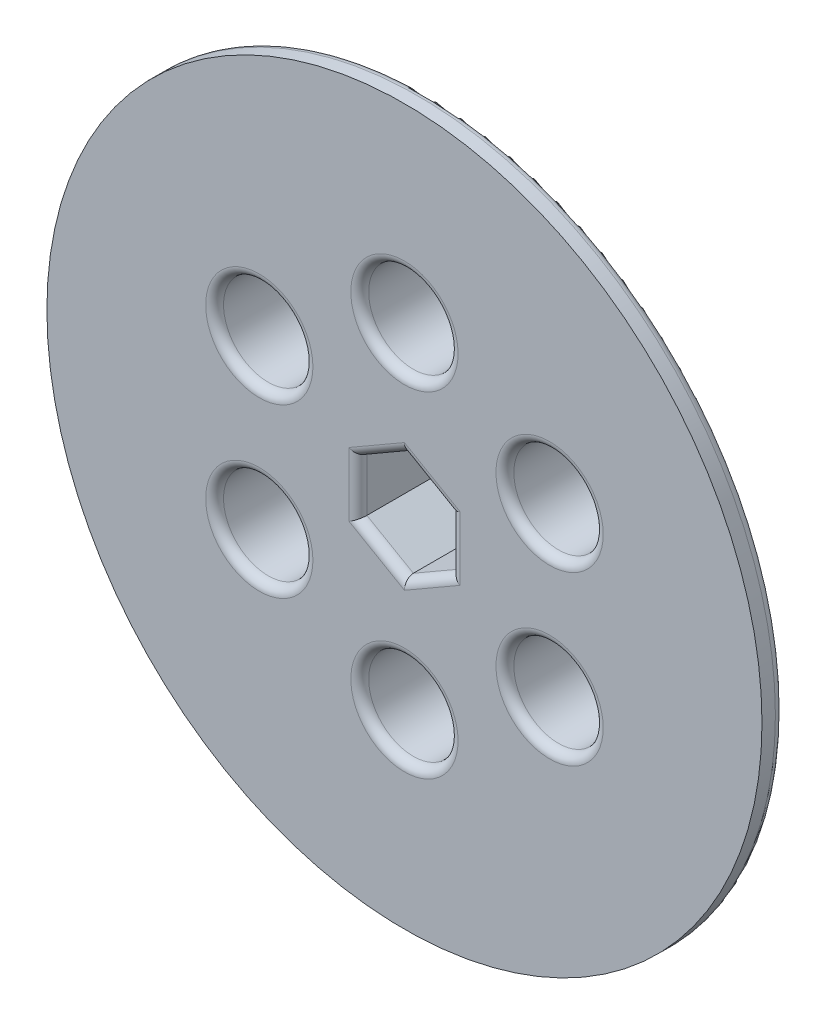
SolidWorks part; units mm, degrees
ref_plane "Front" through (0, 0, 0) normal (0, 0, 1) x (1, 0, 0)
ref_plane "Top" through (0, 0, 0) normal (0, 1, 0) x (1, 0, 0)
ref_plane "Right" through (0, 0, 0) normal (1, 0, 0) x (0, 0, -1)
sketch "Sketch1" plane through (0, 0, 0) normal (0, 0, 1) x (1, 0, 0)
  circle A0 centre (0, 0) radius 31.75
  dimension "D1" = 63.5
extrude "Boss-Extrude1" add sketch "Sketch1" along normal blind 12.7
sketch "Sketch2" plane through (0, 0, 12.7) normal (0, 0, 1) x (1, 0, 0)
  circle A1 centre (0, 0) radius 50.8
  circle A2 centre (0, 0) radius 31.75 construction
  dimension "D1" = 19.05
extrude "Boss-Extrude2" add sketch "Sketch2" along normal blind 3.175
sketch "Sketch3" plane through (0, 0, 0) normal (0, 0, -1) x (-1, 0, 0)
  line L0 (0, 0) -> (0, 23.8125) construction
  line L2 (0, 7.6256) -> (-6.604, 3.8128)
  line L3 (-6.604, 3.8128) -> (-6.604, -3.8128)
  line L4 (-6.604, -3.8128) -> (0, -7.6256)
  line L5 (0, -7.6256) -> (6.604, -3.8128)
  line L6 (6.604, -3.8128) -> (6.604, 3.8128)
  line L7 (6.604, 3.8128) -> (0, 7.6256)
  circle A0 centre (0, 23.8125) radius 2.667
  circle A1 centre (20.6222, 11.9063) radius 2.667
  circle A2 centre (20.6222, -11.9062) radius 2.667
  circle A3 centre (0, -23.8125) radius 2.667
  circle A4 centre (-20.6222, -11.9063) radius 2.667
  circle A5 centre (-20.6222, 11.9062) radius 2.667
  circle A6 centre (0, 0) radius 6.604 construction
  point P17 (0, 0)
  dimension "D2" = 5.334
  dimension "D1" = 23.8125
  dimension "D3" = 6
extrude "r" cut sketch "Sketch3" against normal up to next
sketch "Sketch4" plane through (0, 0, 15.875) normal (0, 0, 1) x (1, 0, 0)
  circle A0 centre (-20.6222, -11.9062) radius 6.35
  circle A1 centre (-20.6222, 11.9063) radius 6.35
  circle A2 centre (0, 23.8125) radius 6.35
  circle A3 centre (20.6222, 11.9062) radius 6.35
  circle A4 centre (20.6222, -11.9063) radius 6.35
  circle A5 centre (0, -23.8125) radius 6.35
  point P15 (0, 0)
  dimension "D1" = 12.7
  dimension "D2" = 6
extrude "Cut-Extrude2" cut sketch "Sketch4" against normal blind 10.16
fillet "Fillet1" radius 1.27 13 edges at (50.8, 0, 12.7) (-14.2722, 11.9063, 15.875) (6.35, 23.8125, 15.875) (26.9722, 11.9062, 15.875) (26.9722, -11.9063, 15.875) (-14.2722, -11.9062, 15.875) (6.35, -23.8125, 15.875) (6.604, 0, 15.875) (3.302, 5.7192, 15.875) (-3.302, 5.7192, 15.875) (-6.604, 0, 15.875) (-3.302, -5.7192, 15.875) (3.302, -5.7192, 15.875)
